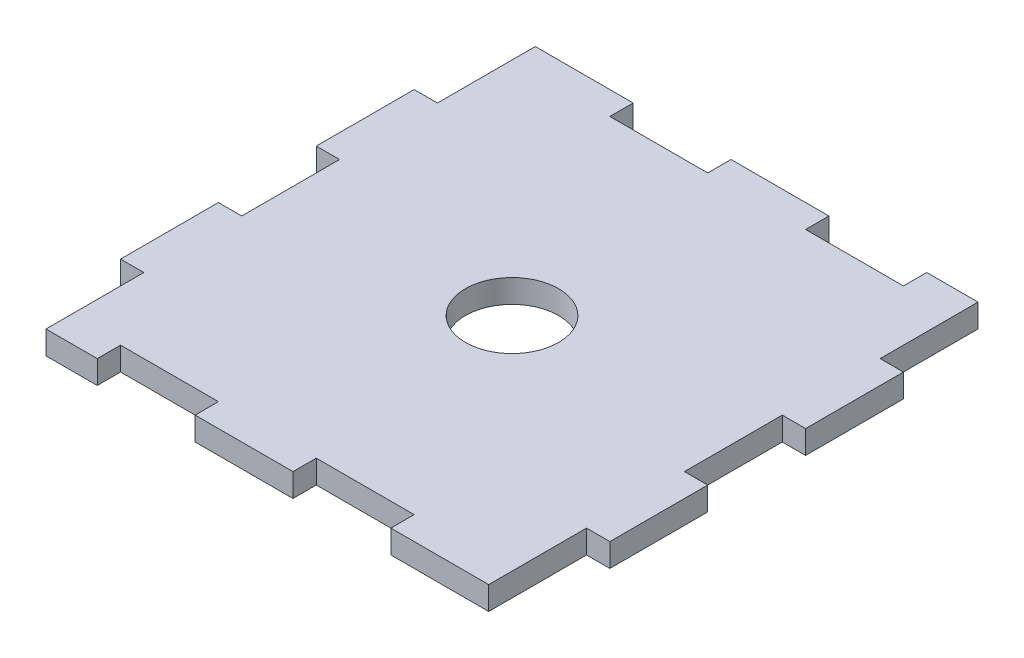
SolidWorks part; units mm, degrees
ref_plane "Front Plane" through (0, 0, 0) normal (0, 0, 1) x (1, 0, 0)
ref_plane "Top Plane" through (0, 0, 0) normal (0, 1, 0) x (1, 0, 0)
ref_plane "Right Plane" through (0, 0, 0) normal (1, 0, 0) x (0, 0, -1)
sketch "Sketch2" plane through (0, 100, 0) normal (0, 1, 0) x (1, 0, 0)
  line L36 (40, 100) -> (40, 95.2375)
  line L37 (40, 95.2375) -> (20, 95.2375)
  line L38 (20, 95.2375) -> (20, 100)
  line L39 (20, 100) -> (0, 100)
  line L40 (0, 100) -> (0, 80)
  line L41 (0, 80) -> (-4.7625, 80)
  line L42 (-4.7625, 80) -> (-4.7625, 60)
  line L43 (-4.7625, 60) -> (0, 60)
  line L44 (0, 60) -> (0, 40)
  line L45 (0, 40) -> (-4.7625, 40)
  line L46 (-4.7625, 40) -> (-4.7625, 20)
  line L47 (-4.7625, 20) -> (0, 20)
  line L48 (0, 20) -> (0, 0)
  line L49 (0, 0) -> (10.475, 0)
  line L50 (10.475, 0) -> (10.475, 4.7625)
  line L51 (10.475, 4.7625) -> (30.475, 4.7625)
  line L52 (30.475, 4.7625) -> (30.475, 0)
  line L53 (30.475, 0) -> (50.475, 0)
  line L54 (50.475, 0) -> (50.475, 4.7625)
  line L55 (50.475, 4.7625) -> (70.475, 4.7625)
  line L56 (70.475, 4.7625) -> (70.475, 0)
  line L57 (70.475, 0) -> (90.475, 0)
  line L58 (90.475, 0) -> (90.475, 20)
  line L59 (90.475, 20) -> (95.2375, 20)
  line L60 (95.2375, 20) -> (95.2375, 40)
  line L61 (95.2375, 40) -> (90.475, 40)
  line L62 (90.475, 40) -> (90.475, 60)
  line L63 (90.475, 60) -> (95.2375, 60)
  line L64 (95.2375, 60) -> (95.2375, 80)
  line L65 (95.2375, 80) -> (90.475, 80)
  line L66 (90.475, 80) -> (90.475, 100)
  line L67 (90.475, 100) -> (80, 100)
  line L68 (80, 100) -> (80, 95.2375)
  line L69 (80, 95.2375) -> (60, 95.2375)
  line L70 (60, 95.2375) -> (60, 100)
  line L71 (60, 100) -> (40, 100)
  line L72 (40, 100) -> (40, 95.2375)
  line L73 (40, 95.2375) -> (20, 95.2375)
  line L74 (20, 95.2375) -> (20, 100)
  line L75 (20, 100) -> (0, 100)
  line L76 (0, 100) -> (0, 80)
  line L77 (0, 80) -> (-4.7625, 80)
  line L78 (-4.7625, 80) -> (-4.7625, 60)
  line L79 (-4.7625, 60) -> (0, 60)
  line L80 (0, 60) -> (0, 40)
  line L81 (0, 40) -> (-4.7625, 40)
  line L82 (-4.7625, 40) -> (-4.7625, 20)
  line L83 (-4.7625, 20) -> (0, 20)
  line L84 (0, 20) -> (0, 0)
  line L85 (0, 0) -> (10.475, 0)
  line L86 (10.475, 0) -> (10.475, 4.7625)
  line L87 (10.475, 4.7625) -> (30.475, 4.7625)
  line L88 (30.475, 4.7625) -> (30.475, 0)
  line L89 (30.475, 0) -> (50.475, 0)
  line L90 (50.475, 0) -> (50.475, 4.7625)
  line L91 (50.475, 4.7625) -> (70.475, 4.7625)
  line L92 (70.475, 4.7625) -> (70.475, 0)
  line L93 (70.475, 0) -> (90.475, 0)
  line L94 (90.475, 0) -> (90.475, 20)
  line L95 (90.475, 20) -> (95.2375, 20)
  line L96 (95.2375, 20) -> (95.2375, 40)
  line L97 (95.2375, 40) -> (90.475, 40)
  line L98 (90.475, 40) -> (90.475, 60)
  line L99 (90.475, 60) -> (95.2375, 60)
  line L100 (95.2375, 60) -> (95.2375, 80)
  line L101 (95.2375, 80) -> (90.475, 80)
  line L102 (90.475, 80) -> (90.475, 100)
  line L103 (90.475, 100) -> (80, 100)
  line L104 (80, 100) -> (80, 95.2375)
  line L105 (80, 95.2375) -> (60, 95.2375)
  line L106 (60, 95.2375) -> (60, 100)
  line L107 (60, 100) -> (40, 100)
  dimension "D1" = 0
extrude "Boss-Extrude1" add sketch "Sketch2" against normal blind 4.7625
sketch "Sketch3" plane through (0, 100, 0) normal (0, 1, 0) x (1, 0, 0)
  circle A0 centre (45.2375, 50) radius 9.525 construction
  circle A1 centre (45.2375, 50) radius 9.525
extrude "Cut-Extrude1" cut sketch "Sketch3" against normal blind 4.7625
